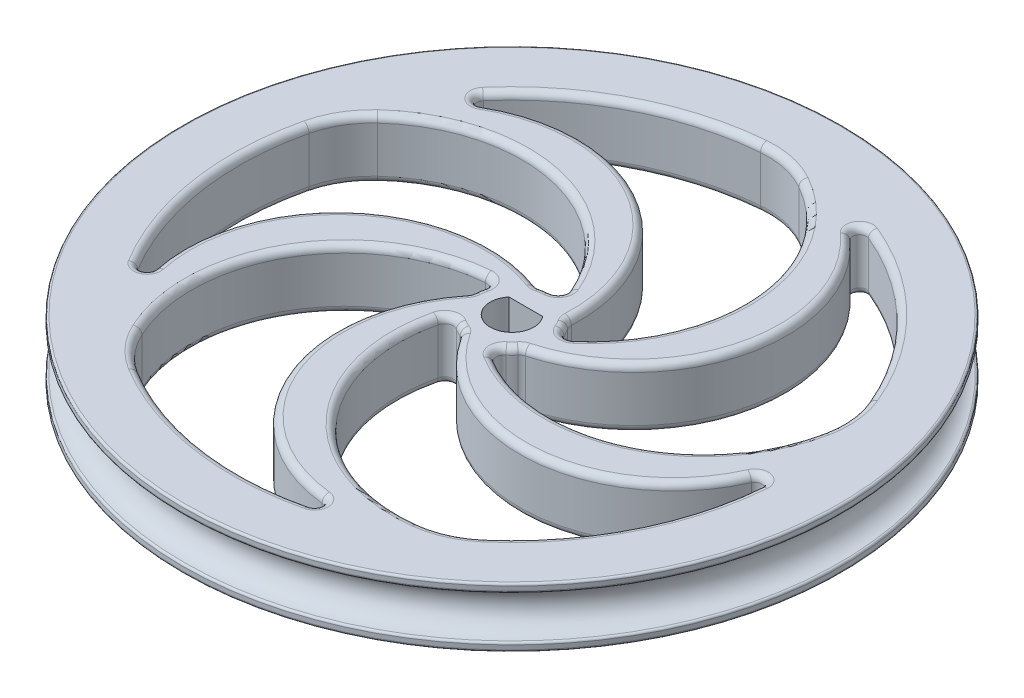
SolidWorks part; units mm, degrees
ref_plane "Front Plane" through (0, 0, 0) normal (0, 0, 1) x (1, 0, 0)
ref_plane "Top Plane" through (0, 0, 0) normal (0, 1, 0) x (1, 0, 0)
ref_plane "Right Plane" through (0, 0, 0) normal (1, 0, 0) x (0, 0, -1)
sketch "Sketch1" plane through (0, 0, 0) normal (0, 0, 1) x (1, 0, 0)
  line L0 (24.5875, 4.445) -> (24.5875, 3.81)
  line L1 (0, 0) -> (24.5875, 0)
  line L2 (0, 0) -> (0, 4.445)
  line L3 (0, 4.445) -> (24.5875, 4.445)
  line L5 (24.5875, 0.635) -> (24.5875, 0)
  arc A0 (24.5875, 3.81) -> (24.5875, 0.635) centre (24.5875, 2.2225) ccw
  dimension "D1" = 1.5875
  dimension "D4" = 180
  dimension "D2" = 4.445
  dimension "D3" = 23
revolve "rim revolve" add sketch "Sketch1" angle 360 about L2
fillet "lip bevel" radius 0.1588 4 edges at (0, 0, -24.5875) (0, 0.635, -24.5875) (0, 3.81, -24.5875) (0, 4.445, -24.5875)
sketch "Sketch3" plane through (0, 4.445, 0) normal (0, 1, 0) x (1, 0, 0)
  line L0 (0, 0) -> (0, 29.6275) construction
  line L1 (0, 0) -> (18.2335, 26.0401) construction
  line L2 (1.2287, -0.8604) -> (20.436, 26.5705) construction
  line L3 (2.4575, -1.7207) -> (20.4848, 24.025) construction
  circle A0 centre (0, 0) radius 20.32
  circle A1 centre (0, 0) radius 3
  arc A3 (0, 20.32) -> (1.2287, -0.8604) centre (-3.6668, 9.4815) cw
  arc A4 (2.4575, -1.7207) -> (4.2248, 19.876) centre (-0.3255, 9.3777) ccw
  arc A5 (19.3255, 6.2792) -> (-0.4386, -1.4345) centre (7.8843, 6.4173) cw
  arc A6 (-0.8771, -2.8689) -> (20.2087, 2.124) centre (8.8181, 3.2075) ccw
  arc A7 (11.9438, -16.4392) -> (-1.4998, -0.0262) centre (8.5396, -5.5154) cw
  arc A8 (-2.9995, -0.0524) -> (8.2649, -18.5632) centre (5.7754, -7.3953) ccw
  arc A9 (-11.9438, -16.4392) -> (-0.4884, 1.4183) centre (-2.6066, -9.8259) cw
  arc A10 (-0.9767, 2.8366) -> (-15.1007, -13.5967) centre (-5.2487, -7.778) ccw
  arc A11 (-19.3255, 6.2792) -> (1.198, 0.9027) centre (-10.1505, -0.5574) cw
  arc A12 (2.3959, 1.8054) -> (-17.5976, 10.16) centre (-9.0193, 2.5883) ccw
  circle A13 centre (0, 0) radius 1.5
  point P18 (2.9947, 0.1785)
  point P45 (0, 0)
  dimension "D1" = 35
  dimension "D2" = 6
  dimension "D3" = 40.64
  dimension "D4" = 12
  dimension "D6" = 3
  dimension "D5" = 5
extrude "spokes" cut sketch "Sketch3" against normal through all contours A12 A1 A3 A0 | A5 A0 A4 A1 | A7 A0 A6 A1 | A9 A0 A8 A1 | A11 A0 A10 A1 region at (7.9885, 4.445, 10.2111) region at (12.18, 4.445, -4.4421) region at (-7.2428, 4.445, 10.753) region at (-0.4609, 4.445, -12.9565) region at (-12.4648, 4.445, -3.5654)
fillet "hub fillet" radius 0.635 10 edges at (2.9947, 2.2225, -0.1785) (0.7556, 2.2225, -2.9033) (-0.9767, 2.2225, -2.8366) (-2.5277, 2.2225, -1.6158) (-2.9995, 2.2225, 0.0524) (-0.8771, 2.2225, 2.8689) (-2.3178, 2.2225, 1.9047) (1.0952, 2.2225, 2.7929) (2.4575, 2.2225, 1.7207) (2.3959, 2.2225, -1.8054)
fillet "spokes to rim obtuse fillet" radius 6.35 5 edges at (0, 2.2225, -20.32) (19.3255, 2.2225, -6.2792) (11.9438, 2.2225, 16.4392) (-11.9438, 2.2225, 16.4392) (-19.3255, 2.2225, -6.2792)
fillet "spokes to rim acute fillet" radius 0.508 5 edges at (-15.1007, 2.2225, 13.5967) (8.2649, 2.2225, 18.5632) (20.2087, 2.2225, -2.124) (4.2248, 2.2225, -19.876) (-17.5976, 2.2225, -10.16)
fillet "hub face fillet" radius 0.508 80 edges at (-16.7447, 4.445, 10.7582) (-12.7001, 4.445, -0.905) (-0.9824, 4.445, -2.8742) (-0.4726, 4.445, -2.9625) (0.35, 4.445, -3.2925) (-7.7196, 4.445, -10.6234) (-19.0866, 4.445, -6.3864) (-20.0673, 4.445, 3.1949) (19.8703, 4.445, 1.1388) (9.7426, 4.445, 8.1971) (-0.8946, 4.445, 2.9027) (-1.359, 4.445, 2.6745) (-2.2185, 4.445, 2.458) (0.001, 4.445, 13.132) (11.6876, 4.445, 16.3855) (18.1127, 4.445, 9.2105) (-15.406, 4.445, -12.6007) (-3.0638, 4.445, -12.3582) (2.4299, 4.445, -1.8225) (2.6715, 4.445, -1.3649) (3.2395, 4.445, -0.6846) (7.718, 4.445, -10.6246) (0.1757, 4.445, -20.1259) (-9.2397, 4.445, -18.0978) (7.2233, 4.445, -18.5458) (10.8066, 4.445, -6.7328) (2.4842, 4.445, 1.7478) (2.1237, 4.445, 2.119) (1.6521, 4.445, 2.8694) (12.4896, 4.445, 4.057) (19.1952, 4.445, -6.0522) (14.3568, 4.445, -14.38) (5.0572, 4.445, 19.2496) (-4.7853, 4.445, 11.7989) (-3.0371, 4.445, 0.0462) (-2.9636, 4.445, -0.466) (-3.0232, 4.445, -1.3503) (-12.4889, 4.445, 4.059) (-11.9719, 4.445, 16.179) (-3.1626, 4.445, 20.0724) (-0.9824, 0, -2.8742) (-12.7001, 0, -0.905) (-16.7447, 0, 10.7582) (-20.0673, 0, 3.1949) (-19.0866, 0, -6.3864) (-7.7196, 0, -10.6234) (0.35, 0, -3.2925) (-0.4726, 0, -2.9625) (-0.8946, 0, 2.9027) (9.7426, 0, 8.1971) (19.8703, 0, 1.1388) (18.1127, 0, 9.2105) (11.6876, 0, 16.3855) (0.001, 0, 13.132) (-2.2185, 0, 2.458) (-1.359, 0, 2.6745) (3.2395, 0, -0.6846) (2.6715, 0, -1.3649) (2.4299, 0, -1.8225) (-3.0638, 0, -12.3582) (-15.406, 0, -12.6007) (-9.2397, 0, -18.0978) (0.1757, 0, -20.1259) (7.718, 0, -10.6246) (2.4842, 0, 1.7478) (10.8066, 0, -6.7328) (7.2233, 0, -18.5458) (14.3568, 0, -14.38) (19.1952, 0, -6.0522) (12.4896, 0, 4.057) (1.6521, 0, 2.8694) (2.1237, 0, 2.119) (-3.0371, 0, 0.0462) (-4.7853, 0, 11.7989) (5.0572, 0, 19.2496) (-3.1626, 0, 20.0724) (-11.9719, 0, 16.179) (-12.4889, 0, 4.059) (-3.0232, 0, -1.3503) (-2.9636, 0, -0.466)
sketch "Sketch2" plane through (0, 4.445, 0) normal (0, 1, 0) x (1, 0, 0)
  line L0 (-1.261, 1.025) -> (1.261, 1.025)
  circle A0 centre (0, 0) radius 1.625
  dimension "D1" = 3.25
  dimension "D2" = 2.65
extrude "axle cut" cut sketch "Sketch2" against normal through all contours L0 A0 region at (0, 4.445, 0.1845)
